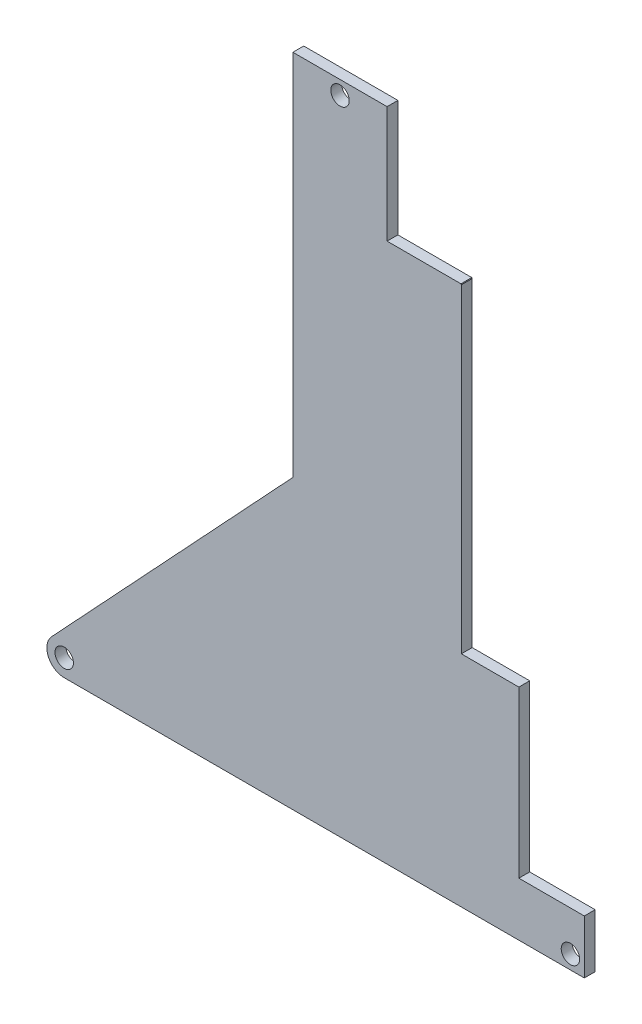
SolidWorks part; units mm, degrees
ref_plane "Front Plane" through (0, 0, 0) normal (0, 0, 1) x (1, 0, 0)
ref_plane "Top Plane" through (0, 0, 0) normal (0, 1, 0) x (1, 0, 0)
ref_plane "Right Plane" through (0, 0, 0) normal (1, 0, 0) x (0, 0, -1)
sketch "Sketch1" plane through (0, 0, 0) normal (0, 0, 1) x (1, 0, 0)
  line L1 (-52.6486, -67.2724) -> (-30.5784, -43.6209)
  line L3 (-30.5784, -43.6209) -> (-18.8373, -31.0385)
  line L4 (-18.8373, 22.9178) -> (-18.8373, 15.0967)
  line L5 (-62.4049, -73.074) -> (-22.4391, -30.2446) construction
  line L6 (-54.2124, -68.9483) -> (-52.6486, -67.2724)
  line L7 (-60.0836, -75.2401) -> (-20.1178, -32.4107) construction
  line L9 (23.8665, -73.2212) -> (-30.5784, -73.2212)
  line L12 (-18.8373, 15.0967) -> (-18.8373, -31.0385)
  line L13 (-30.5784, -73.2212) -> (-52.3554, -73.2212)
  line L14 (-18.8373, 22.9178) -> (-5.0365, 22.9178)
  line L20 (23.8665, -65.3472) -> (23.8665, -73.2212)
  arc A1 (25.454, -65.3472) -> (-3.6178, 23.6674) centre (-125.3585, -65.3472) ccw construction
  arc A2 (23.8665, -65.3472) -> (-5.0365, 22.9178) centre (-125.3585, -65.3472) ccw
  arc A3 (23.8665, -65.3472) -> (-4.8993, 22.7304) centre (-125.3585, -65.3472) ccw construction
  arc A7 (-52.3554, -73.2212) -> (-54.2124, -68.9483) centre (-52.3554, -70.6812) cw
  dimension "D5" = 2.54
  dimension "D1" = 1.5875
  dimension "D2" = 3.175
extrude "Boss-Extrude1" add sketch "Sketch1" along normal blind 1.5875
hole_wizard "#2 Clearance Hole1" positions "Sketch3" profile "Sketch2" hole size "#2" standard "ANSI Inch" end condition through all
sketch "Sketch3" plane through (0, 0, 0) normal (0, 0, -1) x (-1, 0, 0)
  line L0 (11.9369, 20.8858) -> (11.9369, 22.9178) construction
  line L1 (5.0365, 22.9178) -> (18.8373, 22.9178) construction
  line L2 (-23.8665, -73.2212) -> (-23.8665, -65.3472) construction
  line L3 (52.3554, -73.2212) -> (-23.8665, -73.2212) construction
  point P0 (-21.8345, -71.1892)
  point P2 (52.3554, -70.6812)
  point P5 (11.9369, 20.8858)
  dimension "D1" = 2.032
  dimension "D2" = 2.032
  dimension "D3" = 2.032
sketch "Sketch2" plane through (21.8345, -71.1892, 0) normal (1, 0, 0) x (0, 1, 0)
  line L0 (0, 0) -> (0, 1.5875)
  line L1 (0, 1.5875) -> (1.3525, 1.5875)
  line L2 (1.3525, 1.5875) -> (1.3525, 0)
  line L5 (1.3525, 0) -> (0, 0)
  line L11 (0, -6.35) -> (0, 107.95) construction
  dimension "Thru Hole Dia." = 2.7051
  dimension "Thru Hole Depth" = 1.5875
sketch "Sketch4" plane through (0, 0, 0) normal (0, 0, -1) x (-1, 0, 0)
  line L1 (-23.8665, -65.3472) -> (-14.278, -65.3472)
  line L2 (-23.8665, -65.3472) -> (-23.8665, -41.0902)
  line L3 (-23.8665, -41.0902) -> (-14.278, -41.0902)
  line L4 (-14.278, -65.3472) -> (-14.278, -41.0902)
  line L5 (-23.8665, -65.3472) -> (-14.278, -41.0902) construction
  line L6 (-23.8665, -41.0902) -> (-14.278, -65.3472) construction
  line L8 (-14.278, -41.0902) -> (-9.1472, -41.0902) construction
  line L9 (-14.278, -73.9832) -> (-14.278, -41.0902) construction
  line L10 (-5.8452, 5.8452) -> (-21.8817, 5.8452)
  line L11 (-5.8452, 5.8452) -> (-5.8452, -41.0902)
  line L12 (-5.8452, -41.0902) -> (-21.8817, -41.0902)
  line L13 (-21.8817, 5.8452) -> (-21.8817, -41.0902)
  line L14 (-5.8452, 5.8452) -> (-21.8817, -41.0902) construction
  line L15 (-5.8452, -41.0902) -> (-21.8817, 5.8452) construction
  line L16 (5.0365, 22.9178) -> (-5.8452, 22.9178)
  line L17 (5.0365, 22.9178) -> (5.0365, 5.8452)
  line L18 (5.0365, 5.8452) -> (-5.8452, 5.8452)
  line L19 (-5.8452, 22.9178) -> (-5.8452, 5.8452)
  line L20 (5.0365, 22.9178) -> (-5.8452, 5.8452) construction
  line L21 (5.0365, 5.8452) -> (-5.8452, 22.9178) construction
  arc A0 (5.0365, 22.9178) -> (-23.8665, -65.3472) centre (125.3585, -65.3472) ccw construction
  point P4 (-19.0722, -53.2187)
  point P14 (-13.8635, -17.6225)
  point P23 (-0.4043, 14.3815)
  arc M8 (5.0365, 22.9178) -> (-23.8665, -65.3472) centre (125.3585, -65.3472) ccw
extrude "Cut-Extrude1" cut sketch "Sketch4" against normal through all contours L1 L4 L3 M8 | L12 L11 L3 M8 | L18 L17 M8 region at (18.7619, -53.6674, 0) region at (11.7225, -24.2369, 0) region at (-1.3365, 11.675, 0)
